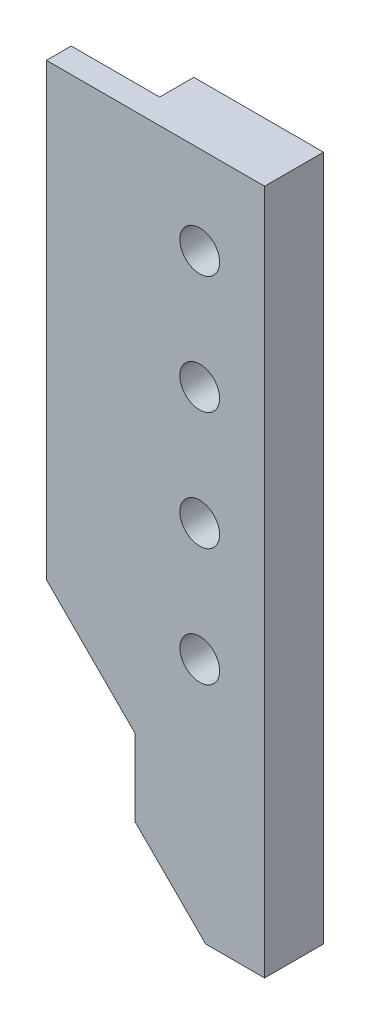
SolidWorks part; units mm, degrees
ref_plane "Front Plane" through (0, 0, 0) normal (0, 0, 1) x (1, 0, 0)
ref_plane "Top Plane" through (0, 0, 0) normal (0, 1, 0) x (1, 0, 0)
ref_plane "Right Plane" through (0, 0, 0) normal (1, 0, 0) x (0, 0, -1)
sketch "Sketch1" plane through (0, 0, 0) normal (0, 0, 1) x (1, 0, 0)
  line L0 (25.2, 31.3209) -> (25.2, -45)
  line L1 (25.2, -45) -> (40.2, -60)
  line L2 (40.2, -60) -> (40.2, 0) construction
  line L3 (40.2, -60) -> (40.2, -85)
  line L5 (62.2, -85) -> (62.2, 31.3209)
  line L6 (62.2, 31.3209) -> (25.2, 31.3209)
  line L12 (40.2, -85) -> (62.2, -85)
  line L13 (40.2, -60) -> (40.2, 31.3209)
  circle A0 centre (0, 0) radius 40.2 construction
  dimension "D1" = 80.4
  dimension "D2" = 15
  dimension "D3" = 15
  dimension "D4" = 60
  dimension "D5" = 25
  dimension "D6" = 22
extrude "Boss-Extrude1" add sketch "Sketch1" along normal blind 4.2 contours L1 L13 L6 L0 | L13 L3 L12 L5 L6 region at (32.9237, -10.7014, 0) region at (51.2, -26.8395, 0)
extrude "Boss-Extrude2" add sketch "Sketch1<3>" against normal blind 5.8 contours L13 L3 L12 L5 L6 region at (51.2, -26.8395, 0)
sketch "Sketch1<3>" plane through (0, 0, 0) normal (0, 0, 1) x (1, 0, 0) same geometry as "Sketch1"
sketch "Sketch2" plane through (0, 0, 4.2) normal (0, 0, 1) x (1, 0, 0)
  line L1 (40.2, -85) -> (62.2, -85) construction
  line L2 (62.2, 31.3209) -> (25.2, 31.3209) construction
  circle A0 centre (51.2, 16.3209) radius 3.375
  point P5 (51.2, -85)
  dimension "D1" = 6.75
  dimension "D2" = 15
extrude "Cut-Extrude1" cut sketch "Sketch2" against normal up to next
ref_axis "Axis1" through (51.2, 16.3209, -5.8) along (0, 0, 1)
ref_plane "Plane1" through (51.2, 0, 0) normal (-1, 0, 0) x (0, 0, 1)
sketch "Sketch3" plane through (51.2, 0, 0) normal (-1, 0, 0) x (0, 0, 1)
  line L0 (4.2, 31.3209) -> (4.2, -45) construction
  line L1 (-5.8, -85) -> (-5.8, 31.3209) construction
  circle A0 centre (-3.8, 19.8959) radius 0.65
  circle A1 centre (2.2, 19.8959) radius 0.65
  dimension "D1" = 1.3
  dimension "D3" = 2
  dimension "D4" = 2
  dimension "D2" = 0.2
pattern_linear "LPattern1" count 4 spacing 20 along (0, -1, 0) of "Cut-Extrude1"
sketch "Sketch4" plane through (0, 0, 4.2) normal (0, 0, 1) x (1, 0, 0)
  line L0 (52.2, -85) -> (40.2, -73)
  line L1 (40.2, -85) -> (62.2, -85) construction
  line L2 (40.2, -85) -> (40.2, -60) construction
  line L3 (40.2, -73) -> (40.2, -85)
  line L4 (40.2, -85) -> (52.2, -85)
  dimension "D1" = 10
  dimension "D2" = 45
extrude "Cut-Extrude2" cut sketch "Sketch4" against normal up to next
ref_plane "Plane2" through (25.2, -45, 0) normal (0, -1, 0) x (-1, 0, 0)
sketch "Sketch6" plane through (25.2, 0, 0) normal (-1, 0, 0) x (0, 0, 1)
  line L0 (4.2, -45) -> (0, -45)
  line L1 (-20.9883, -45) -> (20.9883, -45) construction
  line L2 (4.2, -45) -> (4.2, -60) construction
  line L3 (0, -45) -> (3.7, -60)
  line L4 (4.2, -60) -> (0, -60) construction
  line L5 (3.7, -60) -> (4.2, -60)
  line L6 (4.2, -60) -> (4.2, -45)
  line L8 (4.2, -45) -> (0, -45)
  line L9 (4.2, -45) -> (4.2, -60)
  line L10 (4.2, -60) -> (0, -60)
  line L11 (0, -45) -> (0, -60)
  dimension "D1" = 0.5
extrude "Cut-Extrude3" cut sketch "Sketch6" against normal up to surface (15 mm away) contours L3 L11 L10 region at (25.2, -55, 1.2333) up to face at (40.2, -33.893, -0.5333)
ref_plane "Plane3" through (25.5117, -18.7086, 0) normal (0.8064, -0.5914, 0) x (0, 0, -1)
sketch "Sketch9" plane through (25.5117, -18.7086, 0) normal (0.8064, -0.5914, 0) x (0, 0, -1)
  line L1 (-2.8, 46.8141) -> (-0.6, 46.8141) construction
  line L2 (5.8, 46.8141) -> (-4.2, 46.8141) construction
  line L3 (-4.2, -31.7616) -> (-4.2, 62.0402) construction
  line L5 (-2.9, 47.2937) -> (-0.5, 47.2937) construction
  line L6 (-0.5, 47.2937) -> (-2.9, 47.2937)
  arc A0 (-2.9, 47.2937) -> (-0.5, 47.2937) centre (-1.7, 47.2937) ccw
  point P11 (-1.7, 47.2937)
  dimension "D1" = 2.4
  dimension "D2" = 2.2
  dimension "D3" = 2.5
revolve "Cut-Revolve4" [suppressed] cut sketch "Sketch9" angle 360 about L6
pattern_circular "CirPattern1" [suppressed] count 4 over 360 about axis through (51.2, 16.3209, -5.8) along (0, 0, 1) of bodies 108
pattern_linear "LPattern2" [suppressed] count 4 spacing 20 count 2 spacing 5 of bodies 109
